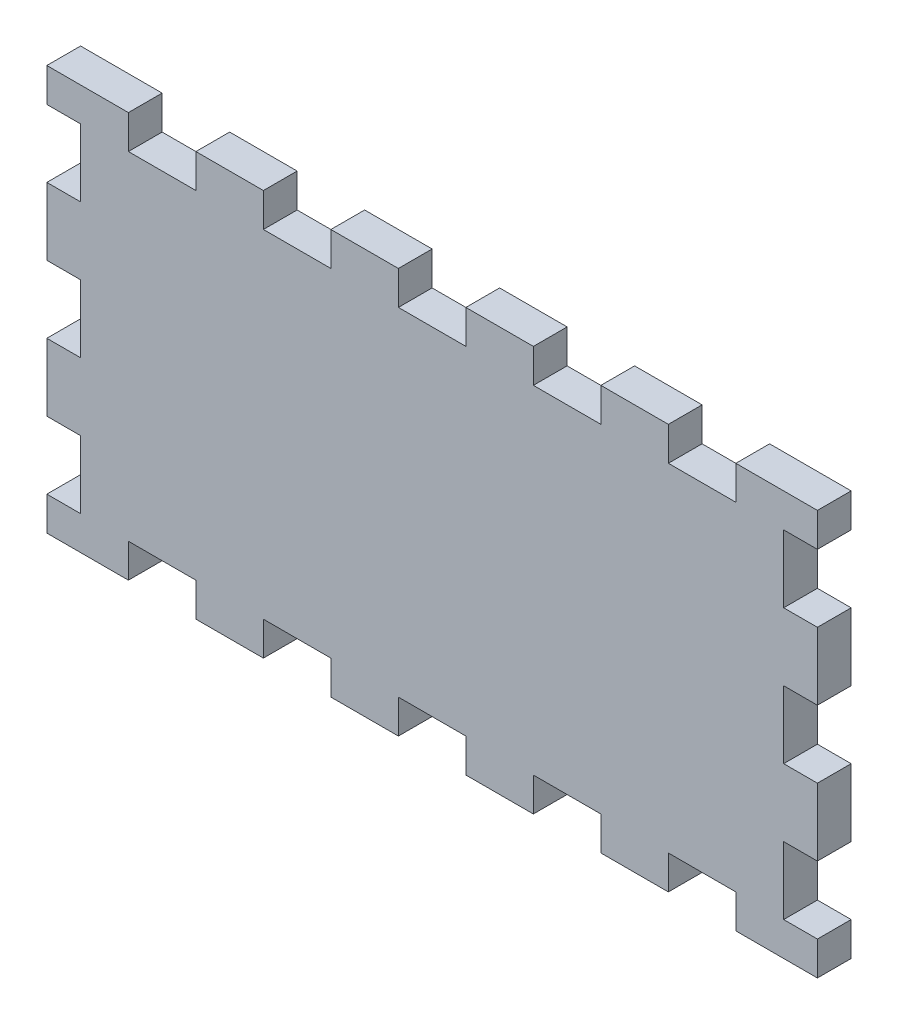
SolidWorks part; units mm, degrees
ref_plane "Front Plane" through (0, 0, 0) normal (0, 0, 1) x (1, 0, 0)
ref_plane "Top Plane" through (0, 0, 0) normal (0, 1, 0) x (1, 0, 0)
ref_plane "Right Plane" through (0, 0, 0) normal (1, 0, 0) x (0, 0, -1)
sketch "Sketch2" plane through (0, 0, 0) normal (0, 0, 1) x (1, 0, 0)
  line L0 (-68.5, 0) -> (-54, 0)
  line L1 (-54, 0) -> (-54, 6)
  line L2 (-54, 6) -> (-42, 6)
  line L3 (-42, 6) -> (-42, 0)
  line L4 (-42, 0) -> (-30, 0)
  line L5 (-30, 0) -> (-30, 6)
  line L6 (-30, 6) -> (-18, 6)
  line L7 (-18, 6) -> (-18, 0)
  line L8 (-18, 0) -> (-6, 0)
  line L9 (-6, 0) -> (-6, 6)
  line L10 (-6, 6) -> (6, 6)
  line L11 (6, 6) -> (6, 0)
  line L12 (6, 0) -> (18, 0)
  line L13 (18, 0) -> (18, 6)
  line L14 (18, 6) -> (30, 6)
  line L15 (30, 6) -> (30, 0)
  line L16 (30, 0) -> (42, 0)
  line L17 (42, 0) -> (42, 6)
  line L18 (42, 6) -> (54, 6)
  line L19 (54, 6) -> (54, 0)
  line L20 (54, 0) -> (68.5, 0)
  line L21 (68.5, 0) -> (68.5, 72)
  line L22 (-68.5, 0) -> (-68.5, 72)
  line L23 (-68.5, 36) -> (68.5, 36)
  line L24 (54, 72) -> (68.5, 72)
  line L25 (54, 66) -> (54, 72)
  line L26 (42, 66) -> (54, 66)
  line L27 (42, 72) -> (42, 66)
  line L28 (30, 72) -> (42, 72)
  line L29 (30, 66) -> (30, 72)
  line L30 (18, 66) -> (30, 66)
  line L31 (18, 72) -> (18, 66)
  line L32 (6, 72) -> (18, 72)
  line L33 (6, 66) -> (6, 72)
  line L34 (-6, 66) -> (6, 66)
  line L35 (-6, 72) -> (-6, 66)
  line L36 (-18, 72) -> (-6, 72)
  line L37 (-18, 66) -> (-18, 72)
  line L38 (-30, 66) -> (-18, 66)
  line L39 (-30, 72) -> (-30, 66)
  line L40 (-42, 72) -> (-30, 72)
  line L41 (-42, 66) -> (-42, 72)
  line L42 (-54, 66) -> (-42, 66)
  line L43 (-54, 72) -> (-54, 66)
  line L44 (-68.5, 72) -> (-54, 72)
  line M1 (-54, 0) -> (-54, 6)
  line M2 (-54, 6) -> (-62.5, 6)
  line M3 (-62.5, 6) -> (-62.5, 0)
  line M4 (-62.5, 0) -> (-54, 0)
  dimension "D1" = 72
extrude "Boss-Extrude1" add sketch "Sketch2" along normal blind 6 contours L44 L22 L23 L21 L24 L25 L26 L27 L28 L29 L30 L31 L32 L33 L34 L35 L36 L37 L38 L39 L40 L41 L42 L43 | L23 L22 L0 L2 L3 L4 L5 L6 L7 L8 L9 L10 L11 L12 L13 L14 L15 L16 L17 L18 L19 L20 L21 M3 M2 | M4 M1 M2 M3 region at (0.6571, 19.3636, 0) region at (-58.25, 3, 0) region at (0, 52.8189, 0)
sketch "Sketch3" plane through (0, 0, 6) normal (0, 0, 1) x (1, 0, 0)
  line L0 (-68.5, 0) -> (-68.5, 72) construction
  line L1 (-68.5, 6) -> (-62.5, 6)
  line L2 (-68.5, 6) -> (-68.5, 18)
  line L3 (-68.5, 18) -> (-62.5, 18)
  line L4 (-62.5, 6) -> (-62.5, 18)
  line L5 (62.5, 6) -> (62.5, 18)
  line L6 (62.5, 6) -> (68.5, 6)
  line L7 (68.5, 6) -> (68.5, 18)
  line L8 (62.5, 18) -> (68.5, 18)
  line L9 (62.5, 30) -> (62.5, 42)
  line L10 (62.5, 30) -> (68.5, 30)
  line L11 (68.5, 30) -> (68.5, 42)
  line L12 (62.5, 42) -> (68.5, 42)
  line L13 (62.5, 54) -> (62.5, 66)
  line L14 (62.5, 54) -> (68.5, 54)
  line L15 (68.5, 54) -> (68.5, 66)
  line L16 (62.5, 66) -> (68.5, 66)
  line L17 (-68.5, 30) -> (-68.5, 42)
  line L18 (-68.5, 30) -> (-62.5, 30)
  line L19 (-62.5, 30) -> (-62.5, 42)
  line L20 (-68.5, 42) -> (-62.5, 42)
  line L21 (-68.5, 54) -> (-68.5, 66)
  line L22 (-68.5, 54) -> (-62.5, 54)
  line L23 (-62.5, 54) -> (-62.5, 66)
  line L24 (-68.5, 66) -> (-62.5, 66)
  line L25 (68.5, 0) -> (68.5, 72) construction
  point P6 (-68.5, 36)
  point P8 (0, 0)
  point P28 (0, 0)
  point P29 (0, 0)
  line M26 (68.5, 0) -> (68.5, 72)
  line M48 (-68.5, 72) -> (-68.5, 0)
  dimension "D1" = 12
  dimension "D2" = 6
  dimension "D5" = 12
  dimension "D3" = 2
  dimension "D4" = 3
extrude "Cut-Extrude1" cut sketch "Sketch3" against normal blind 6 contours L24 L22 L23 M48 | L1 L4 L3 M48 | L12 L9 L10 M26 | L8 L5 L6 M26 | L17 L20 L19 L18 | L13 L16 L15 L14 region at (-65.5, 12, 6) region at (-65.5, 60, 6) region at (65.5, 36, 6) region at (65.5, 12, 6)
